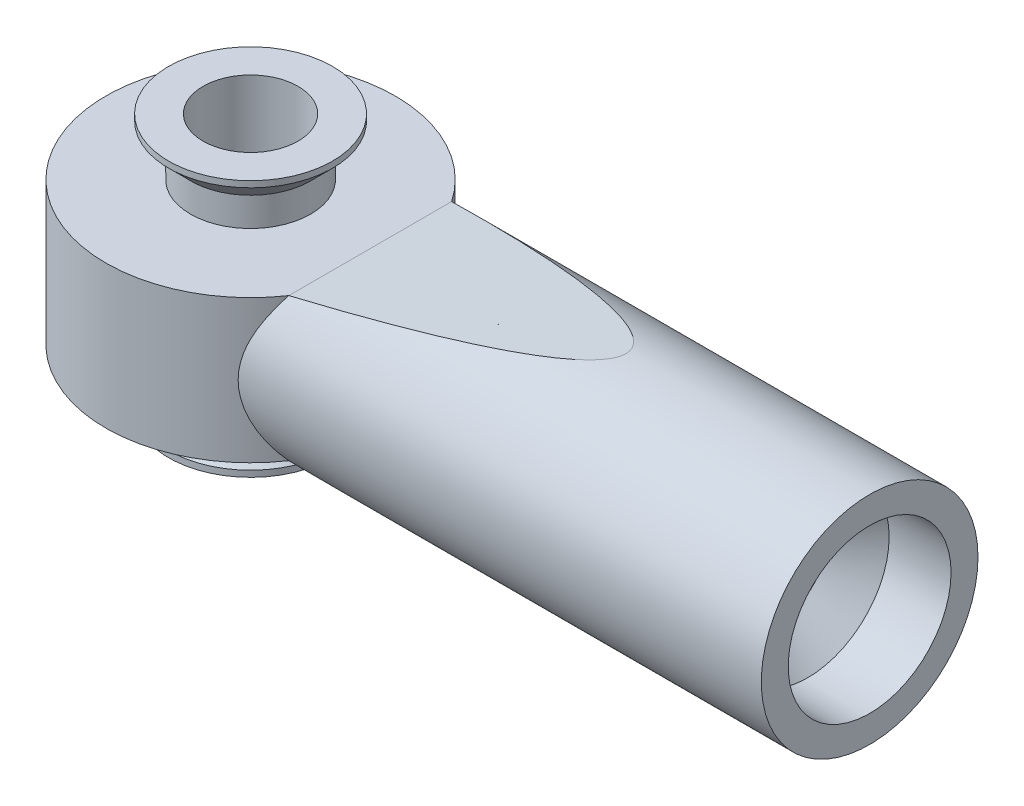
SolidWorks part; units mm, degrees
material "ABS"
ref_plane "Front Plane" through (0, 0, 0) normal (0, 0, 1) x (1, 0, 0)
ref_plane "Top Plane" through (0, 0, 0) normal (0, 1, 0) x (1, 0, 0)
ref_plane "Right Plane" through (0, 0, 0) normal (1, 0, 0) x (0, 0, -1)
sketch "Sketch1" plane through (0, 0, 0) normal (1, 0, 0) x (0, 0, -1)
  circle A0 centre (0, 0) radius 3.5
  circle A1 centre (0, 0) radius 1.6
  circle A2 centre (0, 0) radius 2.63
  dimension "D1" = 1.9
  dimension "D2" = 7
  dimension "D3" = 0.87
extrude "Boss-Extrude1" add sketch "Sketch1" along normal blind 17 contours A0 A2 | A2 A1 region at (0, 0, 3.401) region at (0, 0, 2.5556)
sketch "Sketch2" plane through (0, 0, 0) normal (0, 1, 0) x (1, 0, 0)
  circle A0 centre (0, 0) radius 4.675
  dimension "D1" = 9.35
extrude "Boss-Extrude2" add sketch "Sketch2" along normal mid plane 4.62
sketch "Sketch3" plane through (0, 0, 0) normal (0, 0, 1) x (1, 0, 0)
  line L0 (3.8655, 2.31) -> (-4.675, 2.31) construction
  line L1 (3.8655, 2.31) -> (-4.675, 2.31)
  line L2 (3.8655, 2.31) -> (12.125, 3.5)
  line L3 (17, 3.5) -> (0, 3.5) construction
  dimension "D1" = 16.8
extrude "Cut-Extrude1" cut sketch "Sketch3" against normal through all both and the other way through all
mirror "Mirror1" about plane through (0, 0, 0) normal (0, 1, 0) of "Cut-Extrude1"
extrude "Boss-Extrude3" add sketch "Sketch1<3>" along normal blind 3 from surface contours A0 A2 region at (0, 0, 3.401) starting at face at (17, 0, -3.5)
sketch "Sketch1<3>" plane through (0, 0, 0) normal (1, 0, 0) x (0, 0, -1) same geometry as "Sketch1"
sketch "Sketch4" plane through (0, 0, 0) normal (0, 0, 1) x (1, 0, 0)
  line L0 (0, 4.15) -> (2.65, 4.15)
  line L1 (2.65, 4.15) -> (2.65, 3.95)
  line L2 (2.65, 3.95) -> (1.94, 3.24)
  line L3 (1.94, 3.24) -> (1.94, 2.31)
  line L4 (3.8655, 2.31) -> (-4.675, 2.31) construction
  line L5 (1.94, 2.31) -> (0, 2.31)
  line L6 (0, 2.31) -> (0, 4.15) construction
  line L7 (0, 4.15) -> (0, 2.31)
  dimension "D1" = 4.15
  dimension "D2" = 5.3
  dimension "D3" = 0.2
  dimension "D4" = 3.88
  dimension "D5" = 45
revolve "Revolve1" add sketch "Sketch4" angle 360 about L6
mirror "Mirror2" about plane through (0, 0, 0) normal (0, 1, 0) of "Revolve1"
sketch "Sketch5" plane through (0, 4.15, 0) normal (0, 1, 0) x (1, 0, 0)
  circle A0 centre (0, 0) radius 1.535
  dimension "D1" = 3.07
extrude "Cut-Extrude2" cut sketch "Sketch5" against normal through all
chamfer "Chamfer1" distance 1 angle 45 1 edges at (17, 0, -2.63)
